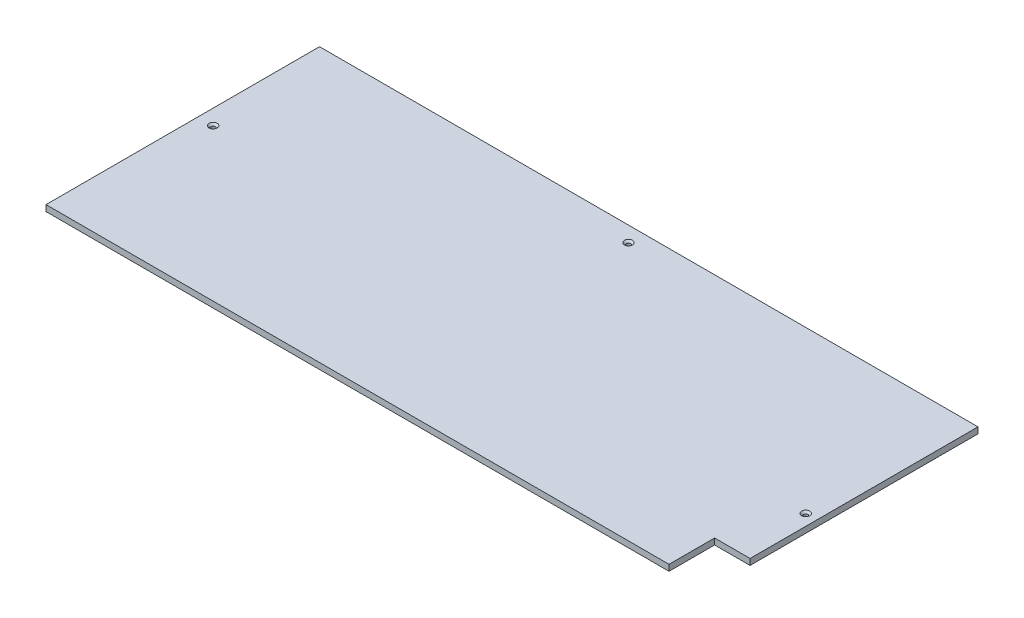
SolidWorks part; units mm, degrees
material "Balsa"
ref_plane "Front Plane" through (0, 0, 0) normal (0, 0, 1) x (1, 0, 0)
ref_plane "Top Plane" through (0, 0, 0) normal (0, 1, 0) x (1, 0, 0)
ref_plane "Right Plane" through (0, 0, 0) normal (1, 0, 0) x (0, 0, -1)
sketch "Sketch1" plane through (0, 0, 0) normal (0, 1, 0) x (1, 0, 0)
  line L1 (325, -150) -> (-325, -150)
  line L2 (325, -150) -> (325, 120)
  line L3 (325, 120) -> (-325, 120)
  line L4 (-325, -150) -> (-325, 120)
  point P0 (0, 0)
  dimension "D1" = 270
  dimension "D2" = 650
extrude "Boss-Extrude1" add sketch "Sketch1" along normal blind 6
sketch "Sketch2" plane through (0, 6, 0) normal (0, 1, 0) x (1, 0, 0)
  line L0 (-325, -150) -> (325, -150) construction
  line L1 (332.7558, 136.8148) -> (290, 136.8148)
  line L2 (332.7558, 136.8148) -> (332.7558, 40)
  line L3 (332.7558, 40) -> (290, 40)
  line L4 (290, 136.8148) -> (290, 40)
  line L5 (-337.1113, -127.8796) -> (-245, -127.8796)
  line L6 (-337.1113, -127.8796) -> (-337.1113, -140)
  line L7 (-337.1113, -140) -> (-245, -140)
  line L8 (-245, -127.8796) -> (-245, -140)
  line L9 (325, -150) -> (325, 120) construction
  line L10 (325, 120) -> (-325, 120) construction
  line L11 (-325, 120) -> (-325, -150) construction
  line L13 (337.9334, -185.1999) -> (290, -185.1999)
  line L14 (337.9334, -185.1999) -> (337.9334, -105)
  line L15 (337.9334, -105) -> (290, -105)
  line L16 (290, -185.1999) -> (290, -105)
  line M6 (-325, -150) -> (325, -150)
  line M7 (325, -150) -> (325, 120)
  dimension "D1" = 10
  dimension "D2" = 35
  dimension "D3" = 80
  dimension "D4" = 80
  dimension "D5" = 35
  dimension "D6" = 45
extrude "Cut-Extrude1" cut sketch "Sketch2" against normal through all contours L16 L15 M6 M7 | L16 L13 L14 L15 M7 M6 region at (318.455, 6, 157.3154) region at (307.5, 6, 127.5)
hole_wizard "CSK for M4 Flat Head Machine Screw1" positions "Sketch4" profile "Sketch5" countersink size "M4" standard "ANSI Metric" end condition through all
sketch "Sketch4" plane through (0, 6, 0) normal (0, 1, 0) x (1, 0, 0)
  line L0 (-325, 120) -> (-325, -150) construction
  line L1 (325, 120) -> (-325, 120) construction
  line L2 (325, -105) -> (325, 120) construction
  point P0 (-310, 0)
  point P2 (-5, 105)
  point P9 (314, -39)
  dimension "D1" = 15
  dimension "D2" = 15
  dimension "D3" = 120
  dimension "D4" = 320
  dimension "D5" = 159
  dimension "D6" = 11
sketch "Sketch5" plane through (-310, 6, 0) normal (1, 0, 0) x (0, 0, 1)
  line L0 (0, 0) -> (0, 6)
  line L1 (0, 6) -> (2.1, 6)
  line L2 (2.1, 6) -> (2.1, 1.9)
  line L3 (2.1, 1.9) -> (4, 0)
  line L5 (4, 0) -> (0, 0)
  line L6 (-2.1, 1.9) -> (-4, 0) construction
  line L11 (0, -6.35) -> (0, 107.95) construction
  dimension "Thru Hole Dia." = 4.2
  dimension "Thru Hole Depth" = 6
  dimension "Near C'Sink Dia." = 8
  dimension "Near C'Sink Angle" = 90
